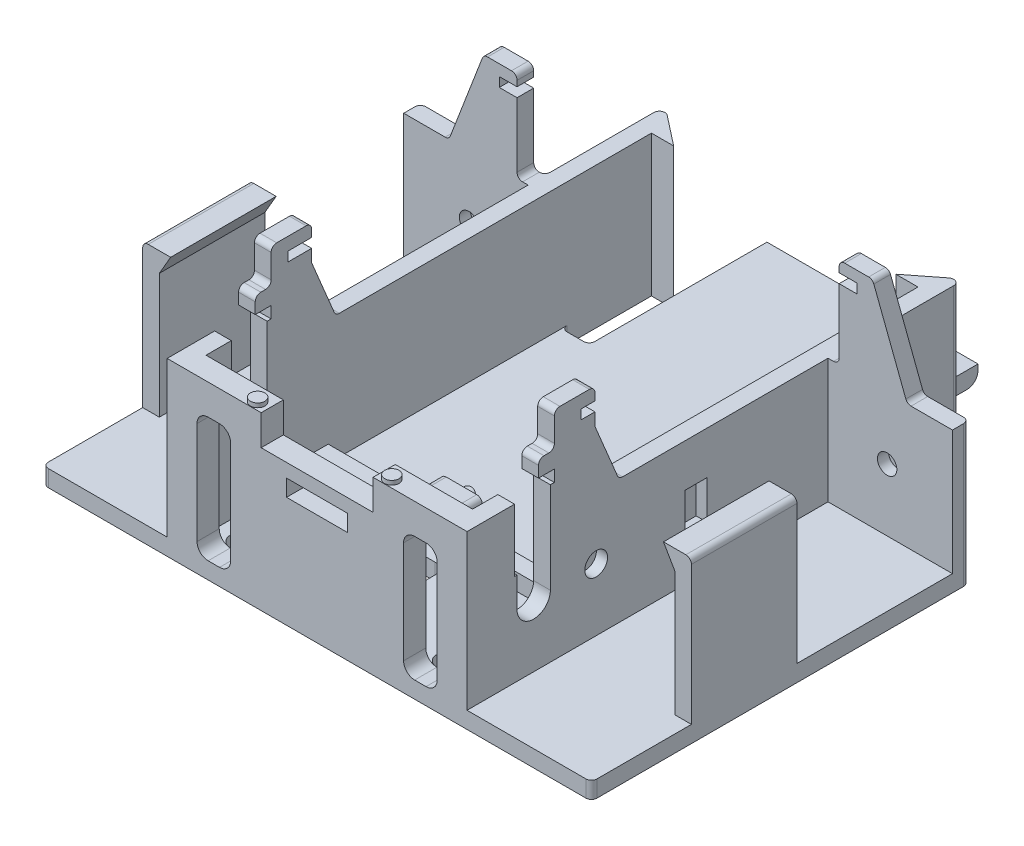
SolidWorks part; units mm, degrees
ref_plane "Front Plane" through (0, 0, 0) normal (0, 0, 1) x (1, 0, 0)
ref_plane "Top Plane" through (0, 0, 0) normal (0, 1, 0) x (1, 0, 0)
ref_plane "Right Plane" through (0, 0, 0) normal (1, 0, 0) x (0, 0, -1)
sketch "Sketch1" plane through (0, 0, 0) normal (0, 1, 0) x (1, 0, 0)
  line L0 (-24, -33.4487) -> (-24, 34.5513)
  line L1 (-24, 34.5513) -> (-49.4, 34.5513)
  line L2 (-49.4, 34.5513) -> (-49.4, 31.5513)
  line L3 (-49.4, 31.5513) -> (-27, 31.5513)
  line L4 (-27, 31.5513) -> (-27, -33.4487)
  line L5 (-27, -33.4487) -> (-24, -33.4487)
  line L6 (0, -12.342) -> (0, 12.342) construction
  line L12 (-27, 34.5513) -> (-24, 34.5513)
  dimension "D1" = 3
  dimension "D2" = 65
  dimension "D4" = 3
  dimension "D5" = 24
extrude "Boss-Extrude1" add sketch "Sketch1" along normal blind 22.4 contours L3 L4 L5 L0 L1 L2
sketch "Sketch3" plane through (0, 0, 0) normal (0, 1, 0) x (1, 0, 0)
  line L0 (-49.4, 34.5513) -> (-49.4, 31.5513) construction
  line L2 (-46.4, 3.5513) -> (-46.4, -15.4487)
  line L3 (-46.4, -15.4487) -> (-49.4, -15.4487)
  line L4 (-49.4, -15.4487) -> (-49.4, 3.5513)
  line L5 (-49.4, 3.5513) -> (-46.4, 3.5513)
  line L6 (-49.4, 31.5513) -> (-27, 31.5513) construction
  dimension "D1" = 28
  dimension "D2" = 19
  dimension "D3" = 3
extrude "Boss-Extrude2" add sketch "Sketch3" along normal blind 22.44 separate body contours L4 L5 L2 L3
sketch "Sketch4" plane through (0, 0, 0) normal (0, 0, 1) x (1, 0, 0)
  line L11 (-46.4, 22.44) -> (-44.3732, 25.9505)
  line L16 (-44.3732, 25.9505) -> (-49.4, 25.9505)
  line L17 (-49.4, 25.9505) -> (-49.4, 22.44)
  line L18 (-49.4, 22.44) -> (-46.4, 22.44)
  line L19 (-49.4, 22.44) -> (-49.4, 0) construction
  line L20 (-49.4, 22.4) -> (-27, 22.4) construction
  dimension "D1" = 60
extrude "Boss-Extrude4" add sketch "Sketch4" along normal blind 19 from surface at -3.5513 starting at face at (-47.9, 11.22, -3.5513)
sketch "Sketch7" plane through (0, 0, 0) normal (1, 0, 0) x (0, 0, -1)
  line L0 (-33.4487, 22.4) -> (-33.4487, 0) construction
  line L2 (-21.4487, 11.22) -> (-21.4487, 27.3779) construction
  line L5 (-24.4487, 11.22) -> (-24.4487, 27.3779)
  line L6 (-18.4487, 11.22) -> (-18.4487, 27.3779)
  arc A4 (-24.4487, 11.22) -> (-18.4487, 11.22) centre (-21.4487, 11.22) ccw
  arc A5 (-18.4487, 27.3779) -> (-24.4487, 27.3779) centre (-21.4487, 27.3779) ccw
  point P1 (-21.4487, 19.299)
  point P2 (-21.4487, 8.22)
  dimension "D1" = 3
  dimension "D2" = 12
sketch "Sketch5" plane through (0, 0, 0) normal (1, 0, 0) x (0, 0, -1)
  line L1 (-33.4487, 22.4) -> (34.5513, 22.4) construction
  line L4 (5.8013, 14.68) -> (9.8013, 14.68)
  line L5 (5.8013, 14.68) -> (5.8013, 7.68)
  line L6 (5.8013, 7.68) -> (9.8013, 7.68)
  line L7 (9.8013, 14.68) -> (9.8013, 7.68)
  circle A1 centre (-10.1987, 11.22) radius 2.05
  dimension "D4" = 4.1
  dimension "D1" = 11.25
  dimension "D2" = 16
  dimension "D7" = 4
  dimension "D8" = 7
  dimension "D9" = 7.72
extrude "Cut-Extrude10" cut sketch "Sketch7" against normal blind 32
extrude "Cut-Extrude2" cut sketch "Sketch5" along normal blind 2 from surface at -27 starting at face at (-27, 13.63, 11.1987)
sketch "Sketch12" plane through (0, 0, 0) normal (0, 1, 0) x (1, 0, 0)
  line L0 (-24, -33.4487) -> (-24, -24.4487) construction
  line L1 (-24, -7.4487) -> (0, -7.4487)
  line L2 (-24, -7.4487) -> (-24, -10.4487)
  line L3 (-24, -10.4487) -> (0, -10.4487)
  line L4 (0, -7.4487) -> (0, -10.4487)
  line L5 (0, -12.342) -> (0, 12.342) construction
  line L6 (-27, -33.4487) -> (-24, -33.4487) construction
  dimension "D1" = 3
  dimension "D3" = 23
extrude "Boss-Extrude7" add sketch "Sketch12" along normal blind 3
sketch "Sketch13" plane through (0, 0, 0) normal (0, 1, 0) x (1, 0, 0)
  line L0 (-49.4, 3.5513) -> (-49.4, 34.5513)
  line L2 (0, 34.5513) -> (0, -10.4487)
  line L3 (0, -12.342) -> (0, 12.342) construction
  line L4 (-24, -10.4487) -> (0, -10.4487) construction
  line L5 (0, -10.4487) -> (-24, -10.4487)
  line L6 (-24, -33.4487) -> (-24, -24.4487) construction
  line L7 (-24, -10.4487) -> (-24, -33.4487)
  line L8 (-24, -33.4487) -> (-49.4, -33.4487)
  line L9 (-49.4, -33.4487) -> (-49.4, -17.4487)
  line L10 (-49.4, -17.4487) -> (-49.4, 3.5513)
  line L11 (-19, 34.5513) -> (-19, 66.5513)
  line L12 (-19, 66.5513) -> (0, 66.5513)
  line L13 (0, 66.5513) -> (0, 34.5513)
  line L14 (-49.4, 34.5513) -> (-19, 34.5513)
  dimension "D1" = 100
  dimension "D2" = 25.4
  dimension "D3" = 5
extrude "Boss-Extrude8" add sketch "Sketch13" against normal blind 3
sketch "Sketch28" plane through (0, 0, 0) normal (0, 0, 1) x (1, 0, 0)
  circle A0 centre (-37.6404, 11.22) radius 1.75
  point P3 (0, 0)
  dimension "D1" = 3.5
extrude "Cut-Extrude5" cut sketch "Sketch28" against normal blind 2 from surface at -31.5513 starting at face at (-38.2, 11.2, -31.5513)
sketch "Sketch41" plane through (0, 0, 0) normal (0, 1, 0) x (1, 0, 0)
  line L0 (-27, 34.5513) -> (-27, 56.2324)
  line L1 (-24, 34.5513) -> (-49.4, 34.5513) construction
  line L4 (-24, 50.7513) -> (-24, 34.5513)
  line L5 (-24, 34.5513) -> (-27, 34.5513)
  line L6 (-27, 56.2324) -> (-20, 50.7513)
  line L7 (-20, 50.7513) -> (-24, 50.7513)
  line L8 (0, -7.4487) -> (-24, -7.4487) construction
  line L9 (-19, 66.5513) -> (-19, 34.5513) construction
  line L10 (-27, 31.5513) -> (-27, -33.4487) construction
  point P4 (-27, 56.2324)
  dimension "D1" = 58.2
  dimension "D2" = 1
extrude "Boss-Extrude21" add sketch "Sketch41" against normal up to surface (25.4 mm away) from surface
sketch "Sketch44" plane through (0, 0, 0) normal (0, 0, 1) x (1, 0, 0)
  line L0 (-27, 22.4) -> (-49.4, 22.4) construction
  line L1 (-29, 22.4) -> (-35, 22.4)
  line L3 (-29, 38.7213) -> (-35, 38.7213)
  line L5 (-32, 38.7213) -> (-32, 22.4) construction
  line L6 (0, 15.4) -> (0, -15.4) construction
  line L7 (-35, 38.7213) -> (-41.2551, 22.4)
  line L8 (-49.4, 22.4) -> (-27, 22.4) construction
  line L9 (-41.2551, 22.4) -> (-35, 22.4)
  line L10 (-29, 36.7213) -> (-32.2, 36.7213)
  line L11 (-32.2, 36.7213) -> (-32.2, 35.0213)
  line L12 (-32.2, 35.0213) -> (-29, 35.0213)
  line L13 (-29, 38.7213) -> (-29, 36.7213)
  line L14 (-29, 35.0213) -> (-29, 22.4)
  line L15 (-24.847, 35.1213) -> (-32.0806, 35.1213) construction
  line L16 (-24.847, 36.6213) -> (-32.0806, 36.6213) construction
  dimension "D1" = 32
  dimension "D2" = 0.2
  dimension "D3" = 0.1
  dimension "D4" = 0.1
  dimension "D5" = 2
extrude "Boss-Extrude23" add sketch "Sketch44" against normal up to surface (3 mm away) from surface
sketch "Sketch45" plane through (-2.5551, -1.7941, 4.0219) normal (1, 0, 0) x (0, 0, -1)
  line L3 (-6.4037, 34.5534) -> (-2.0889, 24.1941)
  line L4 (-14.4267, 24.1941) -> (54.7733, 24.1941) construction
  line L6 (-14.4267, 24.1941) -> (-6.387, 24.1941)
  line L7 (-2.0889, 24.1941) -> (-6.387, 24.1941)
  line L8 (-6.4037, 40.825) -> (-6.4037, 34.5534)
  line L9 (-16.5641, 34.5534) -> (-13.7017, 34.5534)
  line L10 (-20.4267, 24.1941) -> (-29.4267, 24.1941) construction
  line L12 (-13.7017, 34.5534) -> (-13.7017, 40.825)
  line L13 (-16.5641, 31.5599) -> (-13.7017, 31.5599)
  line L14 (-13.7017, 31.5599) -> (-13.7017, 29.4599)
  line L15 (-13.7017, 29.4599) -> (-14.4267, 29.4599)
  line L17 (-14.4267, 29.4599) -> (-14.4267, 24.1941)
  line L18 (-21.2017, 29.6599) -> (-13.9017, 29.6599) construction
  line L19 (-13.9017, 31.3599) -> (-21.2017, 31.3599) construction
  line L20 (-13.9017, 29.6599) -> (-13.9017, 31.3599) construction
  line L23 (-16.5641, 34.5534) -> (-16.5641, 31.5599)
  line L24 (-13.7017, 40.825) -> (-6.4037, 40.825)
  dimension "D1" = 0.2
  dimension "D2" = 0.2
  dimension "D3" = 0.2
extrude "Boss-Extrude25" add sketch "Sketch45" against normal up to surface (3 mm away) from surface at -21.4449 up to face at (-27, 13.63, 11.1987) starting at face at (-24, 7.36, 1.2773)
sketch "Sketch51" plane through (-27, 0, 0) normal (-1, 0, 0) x (0, 0, 1)
  line L0 (24.4487, 16.5658) -> (24.8987, 16.5658)
  line L1 (24.4487, 22.4) -> (24.4487, 11.22) construction
  line L2 (24.8987, 16.5658) -> (24.8987, 22.4)
  line L3 (24.4487, 22.4) -> (33.4487, 22.4) construction
  line L4 (24.8987, 22.4) -> (24.0848, 22.4)
  line L5 (24.0848, 22.4) -> (24.0848, 16.5658)
  line L6 (24.0848, 16.5658) -> (24.4487, 16.5658)
  line L7 (24.6987, 16.7658) -> (18.4487, 16.7658) construction
  line L8 (24.6987, 16.7658) -> (24.6987, 25.2658) construction
  dimension "D1" = 0.2
  dimension "D2" = 0.2
extrude "Cut-Extrude16" cut sketch "Sketch51" against normal blind 10 from surface at 0 starting at face at (-27, 23.5437, 13.4481)
mirror "Mirror1" about plane through (0, 0, 0) normal (1, 0, 0) of bodies 169 120
fillet "Fillet8" radius 1 8 edges at (49.4, 9.7, -34.5513) (49.4, -1.5, 33.4487) (27, 9.7, -56.2324) (27, 9.7, -34.5513) (-49.4, -1.5, 33.4487) (-49.4, 9.7, -34.5513) (-27, 9.7, -34.5513) (-27, 9.7, -56.2324)
fillet "Fillet10" radius 1 4 edges at (24, -1.5, -34.5513) (19, -1.5, -34.5513) (-19, -1.5, -34.5513) (-24, -1.5, -34.5513)
fillet "Fillet11" radius 1 2 edges at (-49.4, 25.9505, 5.9487) (49.4, 25.9505, 5.9487)
fillet "Fillet12" radius 2 1 edges at (0, -3, -66.5513)
sketch "Sketch17" plane through (0, 0, 0) normal (0, 1, 0) x (1, 0, 0)
  line L0 (-24, -33.4487) -> (-24, -24.8987) construction
  line L1 (-24, -29.4487) -> (24, -29.4487)
  line L2 (-24, -29.4487) -> (-24, -33.4487)
  line L3 (-24, -33.4487) -> (24, -33.4487)
  line L4 (24, -29.4487) -> (24, -33.4487)
  dimension "D1" = 4
extrude "Boss-Extrude9" add sketch "Sketch17" along normal up to surface (25.4 mm away) from surface
sketch "Sketch38" plane through (0, 0, 0) normal (1, 0, 0) x (0, 0, -1)
  line L0 (-10.4487, 3) -> (-10.4487, 8.5)
  line L1 (-10.4487, 8.5) -> (-7.4487, 8.5)
  line L2 (-7.4487, 8.5) -> (-7.4487, 3)
  line L3 (-7.4487, 3) -> (-7.4487, 0) construction
  line L4 (-10.4487, 3) -> (-7.4487, 3)
  dimension "D1" = 5.5
extrude "Boss-Extrude19" add sketch "Sketch38" along normal mid plane 7.5
sketch "Sketch39" plane through (0, 0, 0) normal (0, 0, 1) x (1, 0, 0)
  line L0 (0, -12.342) -> (0, 12.342) construction
  line L1 (36.96, 0) -> (-36.96, 0) construction
  circle A0 centre (0, 6) radius 1.5
  dimension "D2" = 3
  dimension "D1" = 6
extrude "Boss-Extrude20" add sketch "Sketch39" against normal blind 3 from surface at 7.4487 starting at face at (0, 3.625, 7.4487)
sketch "Sketch40" plane through (0, 0, 0) normal (1, 0, 0) x (0, 0, -1)
  line L0 (-7.4487, 4.5) -> (-4.4487, 9.6962)
  line L1 (-4.4487, 4.5) -> (-4.4487, 7.5) construction
  line L2 (-4.4487, 9.6962) -> (-4.4487, 4.5)
  line L3 (-4.4487, 4.5) -> (-7.4487, 4.5)
  dimension "D1" = 60
extrude "Cut-Extrude7" cut sketch "Sketch40" against normal blind 9 from surface at 3.75 starting at face at (3.75, 5.75, 8.9487)
sketch "Sketch42" plane through (0, 0, 0) normal (0, 1, 0) x (1, 0, 0)
  line L1 (-24, -10.4487) -> (24, -10.4487)
  line L2 (-24, -10.4487) -> (-24, -29.4487)
  line L3 (-24, -29.4487) -> (24, -29.4487)
  line L4 (24, -10.4487) -> (24, -29.4487)
extrude "Boss-Extrude22" add sketch "Sketch42" against normal blind 3
fillet "Fillet9" radius 1 4 edges at (-3.75, 3, 8.9487) (-3.75, 8.5, 8.9487) (3.75, 3, 8.9487) (3.75, 8.5, 8.9487)
sketch "Sketch46" plane through (-2.5551, -1.7941, 4.0219) normal (1, 0, 0) x (0, 0, -1)
  line L0 (-6.4037, 38.5154) -> (-8.9462, 38.5154)
  line L1 (-6.4037, 40.825) -> (-6.4037, 34.5534) construction
  line L2 (-8.9462, 38.5154) -> (-8.9462, 36.8154)
  line L3 (-8.9462, 36.8154) -> (-6.4037, 36.8154)
  line L4 (-6.4037, 38.5154) -> (-6.4037, 36.8154)
  line L5 (-42.3677, 38.4154) -> (97.8214, 38.4154) construction
  line L6 (-4.2094, 36.9154) -> (-9.7418, 36.9154) construction
  dimension "D1" = 0.1
  dimension "D2" = 0.1
extrude "Cut-Extrude11" cut sketch "Sketch46" against normal blind 10 from surface at 21.5551
sketch "Sketch47" plane through (-2.5551, -1.7941, 4.0219) normal (1, 0, 0) x (0, 0, -1)
  line L0 (-6.4037, 40.825) -> (-6.4037, 34.5534) construction
  line L1 (-6.4037, 36.8154) -> (-10.0956, 36.8154)
  line L2 (-6.4037, 36.8154) -> (-6.4037, 38.5154)
  line L3 (-6.4037, 38.5154) -> (-10.0956, 38.5154)
  line L4 (-10.0956, 36.8154) -> (-10.0956, 38.5154)
  line L5 (-42.3677, 38.4154) -> (97.8214, 38.4154) construction
  line L6 (-9.8212, 36.9154) -> (63.841, 36.9154) construction
  dimension "D1" = 0.1
  dimension "D2" = 0.1
extrude "Cut-Extrude12" cut sketch "Sketch47" along normal blind 8 from surface at -24.4449 starting at face at (-27, 22.8092, 14.6535)
sketch "Sketch48" plane through (0, 0, 0) normal (0, 1, 0) x (1, 0, 0)
  line L1 (-24.847, -13.8431) -> (-32.0806, -13.8431) construction
  line L3 (-22.5092, -16.1809) -> (-24.847, -13.8431) construction
  line L4 (-24.847, -13.8431) -> (-23.6781, -15.012)
  line L7 (-24.847, -13.8431) -> (-22.9907, -13.8431)
  line L8 (-22.9907, -13.8431) -> (-22.9907, -15.012)
  line L9 (-22.9907, -15.012) -> (-23.6781, -15.012)
  line L10 (27.9205, -11.7924) -> (25.7069, -13.7637)
  line L11 (31.9194, -8.2313) -> (25.7069, -13.7637) construction
  line L12 (25.7069, -13.7637) -> (14.2384, -13.7637) construction
  line L13 (25.7069, -13.7637) -> (23.3638, -13.7637)
  line L14 (23.3638, -13.7637) -> (23.3638, -11.7924)
  line L15 (23.3638, -11.7924) -> (27.9205, -11.7924)
extrude "Cut-Extrude13" cut sketch "Sketch48" along normal up to surface (1.7 mm away) from surface at 35.0213 up to face at (-25.5, 36.7213, 12.2715) starting at face at (-25.5, 35.0213, 12.2715)
sketch "Sketch49" plane through (0, 0, 33.4487) normal (0, 0, 1) x (1, 0, 0)
  line L1 (-21.6203, 0) -> (-15.5703, 0)
  line L2 (-21.6203, 0) -> (-21.6203, 22.4)
  line L3 (-21.6203, 22.4) -> (-15.5703, 22.4)
  line L4 (-15.5703, 0) -> (-15.5703, 22.4)
  line L7 (-18.5953, 22.4) -> (-18.5953, 0) construction
  line L8 (-21.1203, 24.384) -> (-21.1203, -1.366) construction
  line L9 (-18.5703, -1.366) -> (-18.5703, 24.384) construction
  dimension "D1" = 0.5
  dimension "D2" = 3
extrude "Cut-Extrude14" cut sketch "Sketch49" against normal blind 10
sketch "Sketch50" plane through (-0.2447, 36.6213, -23.7049) normal (0, -1, 0) x (0, 0, -1)
  line L0 (-53.1536, -15.3256) -> (-57.1536, -15.3256) construction
  line L1 (-53.1536, -15.3256) -> (-36.9336, -15.3256)
  line L2 (-53.1536, -15.3256) -> (-53.1536, -21.3756)
  line L3 (-53.1536, -21.3756) -> (-36.9336, -21.3756)
  line L4 (-36.9336, -15.3256) -> (-36.9336, -21.3756)
  line L5 (-53.1536, -21.3756) -> (-57.1536, -21.3756) construction
  line L6 (-53.1536, -15.3256) -> (-53.1536, 24.2447) construction
  line L7 (-45.0436, -18.3256) -> (-45.0436, -23.3053) construction
  line L8 (-11.3629, 0.2447) -> (-36.0469, 0.2447) construction
  line L9 (-53.1536, -2.7803) -> (-36.9336, -2.7803)
  line L10 (-53.1536, -2.7803) -> (-53.1536, 3.2697)
  line L11 (-53.1536, 3.2697) -> (-36.9336, 3.2697)
  line L12 (-36.9336, -2.7803) -> (-36.9336, 3.2697)
  line L13 (-53.1536, -2.7803) -> (-36.9336, 3.2697) construction
  line L14 (-53.1536, 3.2697) -> (-36.9336, -2.7803) construction
  point P13 (-45.0436, 0.2447)
  dimension "D1" = 8.11
  dimension "D2" = 6.05
extrude "Cut-Extrude15" cut sketch "Sketch50" against normal blind 10 from surface at 39.6213 starting at face at (0, -3, -32.5065)
sketch "Sketch52" plane through (0, 22.4, 0) normal (0, 1, 0) x (1, 0, 0)
  line L0 (-27, -24.8987) -> (-27, -33.4487)
  line L1 (-27, -33.4487) -> (-10.0749, -33.4487)
  line L2 (-15.5703, -33.4487) -> (27, -33.4487) construction
  line L3 (-10.0749, -25.2237) -> (-10.0749, -41.0837) construction
  line L4 (-10.0749, -33.4487) -> (-10.0749, -29.4487)
  line L5 (-15.5703, -29.4487) -> (24, -29.4487) construction
  line L6 (-10.0749, -29.4487) -> (-24, -29.4487)
  line L7 (-24, -29.4487) -> (-24, -24.8987)
  line L8 (-24, -29.4487) -> (-24, -24.8987) construction
  line L9 (-24, -24.8987) -> (-27, -24.8987) construction
  line L10 (-24, -24.8987) -> (-27, -24.8987)
extrude "Boss-Extrude27" add sketch "Sketch52" along normal up to surface (5.4658 mm away)
mirror "Mirror2" about plane through (0, 0, 0) normal (1, 0, 0) of "Boss-Extrude27", "Cut-Extrude14", "Cut-Extrude15"
fillet "Fillet13" radius 1 18 edges at (-29, 38.7213, -33.0513) (-35, 38.7213, -33.0513) (-41.2551, 22.4, -33.0513) (-29, 22.4, -33.0513) (-25.5, 32.7593, 20.586) (-25.5, 32.7593, 17.7237) (-25.5, 39.0309, 17.7237) (-25.5, 39.0309, 10.4256) (-25.5, 22.4, 6.1109) (29, 22.4, -33.0513) (29, 38.7213, -33.0513) (35, 38.7213, -33.0513) (41.2551, 22.4, -33.0513) (25.5, 32.7593, 20.586) (25.5, 32.7593, 17.7237) (25.5, 39.0309, 17.7237) (25.5, 39.0309, 10.4256) (25.5, 22.4, 6.1109)
fillet "Fillet14" radius 2 8 edges at (-15.5703, 0, 31.4487) (-21.6203, 0, 31.4487) (-21.6203, 22.4, 31.4487) (-15.5703, 22.4, 31.4487) (21.6203, 22.4, 31.4487) (15.5703, 22.4, 31.4487) (21.6203, 0, 31.4487) (15.5703, 0, 31.4487)
fillet "Fillet15" radius 2 12 edges at (21.6203, -1.5, 13.2287) (21.6203, -1.5, 29.4487) (15.5703, -1.5, 29.4487) (15.5703, -1.5, 13.2287) (-3.025, -1.5, 13.2287) (3.025, -1.5, 13.2287) (3.025, -1.5, 29.4487) (-3.025, -1.5, 29.4487) (-15.5703, -1.5, 29.4487) (-21.6203, -1.5, 29.4487) (-15.5703, -1.5, 13.2287) (-21.6203, -1.5, 13.2287)
sketch "Sketch53" plane through (-0.2447, 36.6213, -23.7049) normal (0, -1, 0) x (0, 0, -1)
  circle A0 centre (-55.7786, -11.8302) radius 1.3
  circle A1 centre (-55.7786, 12.3196) radius 1.3
  dimension "D1" = 2.6
  dimension "D2" = 2.6
extrude "Boss-Extrude28" add sketch "Sketch53" against normal blind 0.75 from surface at 8.7555 starting at face at (-20.3583, 27.8658, 29.2653)
sketch "Sketch54" plane through (0, 0, 0) normal (0, 0, 1) x (1, 0, 0)
  line L0 (0, -12.342) -> (0, 12.342) construction
  line L1 (-5.5, 19.9561) -> (5.5, 19.9561)
  line L2 (-5.5, 19.9561) -> (-5.5, 16.9561)
  line L3 (-5.5, 16.9561) -> (5.5, 16.9561)
  line L4 (5.5, 19.9561) -> (5.5, 16.9561)
  line L5 (-5.5, 19.9561) -> (5.5, 16.9561) construction
  line L6 (-5.5, 16.9561) -> (5.5, 19.9561) construction
  point P0 (0, 18.4561)
  point P7 (0, 18.4561)
  dimension "D1" = 3
  dimension "D2" = 11
extrude "Cut-Extrude17" cut sketch "Sketch54" against normal blind 10 from surface at 33.4487 starting at face at (0, 12.5219, 33.4487)
